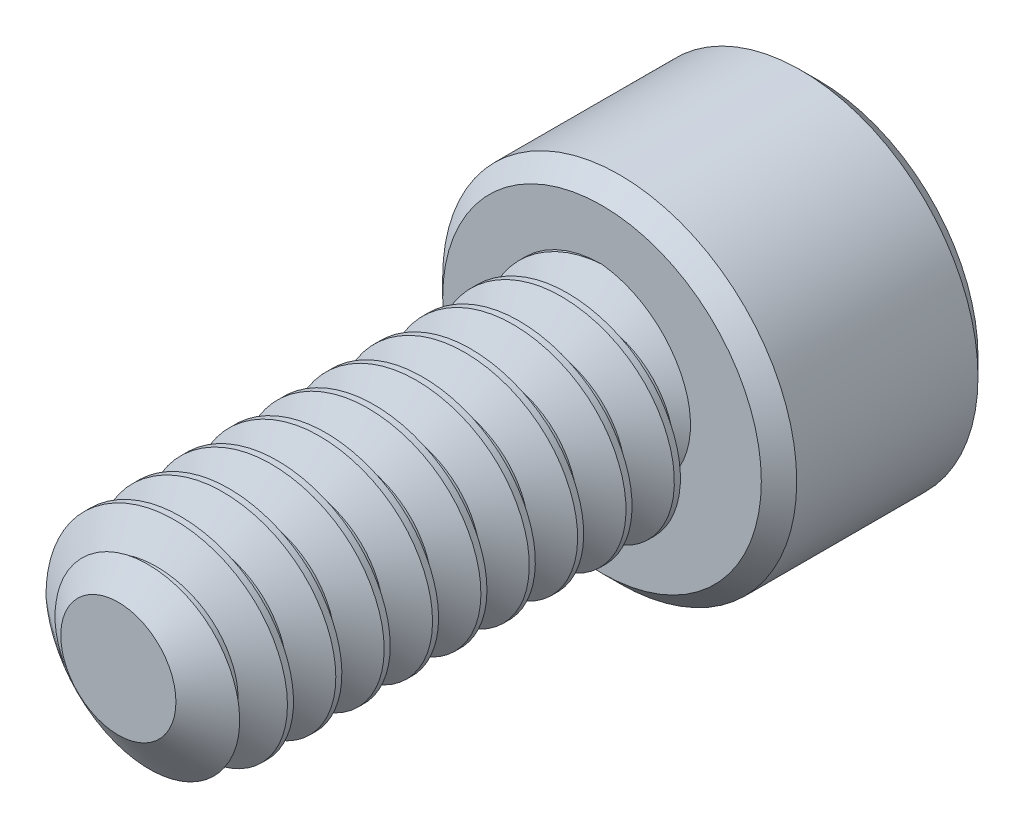
SolidWorks part; units mm, degrees
ref_plane "Front Plane" through (0, 0, 0) normal (0, 0, 1) x (1, 0, 0)
ref_plane "Top Plane" through (0, 0, 0) normal (0, 1, 0) x (1, 0, 0)
ref_plane "Right Plane" through (0, 0, 0) normal (1, 0, 0) x (0, 0, -1)
sketch "Sketch1" plane through (0, 0, 0) normal (0, 0, 1) x (1, 0, 0)
  circle A0 centre (0, 0) radius 1.4224
  dimension "OD" = 2.8448
extrude "Extrude1" add sketch "Sketch1" against normal blind 6.35
sketch "Sketch2" plane through (0, 0, 0) normal (0, 0, 1) x (1, 0, 0)
  circle A0 centre (0, 0) radius 1.4224 construction
  circle A1 centre (0, 0) radius 1.4224
curve "Helix/Spiral1" pitch 0.635 height 6.985 radius 1.4224 centre (0, 0, 0) axis (0, 0, -1) start towards (0, 1, 0) parameters "pitch"=0.635
sketch "Sketch3" plane through (0, 0, 0) normal (1, 0, 0) x (0, 0, -1)
  line L0 (-0.5556, 1.4224) -> (-0.3175, 1.01)
  line L1 (-0.3175, 1.01) -> (-0.2381, 1.01)
  line L2 (-0.2381, 1.01) -> (0, 1.4224)
  line L3 (-0.5556, 1.4224) -> (0, 1.4224)
  line L4 (-0.2778, 1.4224) -> (-0.2778, 1.01) construction
  line L5 (-0.4366, 1.2162) -> (-0.1191, 1.2162) construction
  line L6 (0, 1.4224) -> (0, -1.4224) construction
  dimension "D1" = 0.0794
  dimension "D2" = 0.3175
  dimension "D3" = 60
sweep "Cut-Sweep1" cut profiles "Sketch3" path "Helix/Spiral1"
sketch "Sketch4" plane through (0, 0, 0) normal (1, 0, 0) x (0, 0, -1)
  line L0 (0.4666, 1.4224) -> (0, 0.756)
  line L1 (0, 0.756) -> (0, 1.4224)
  line L2 (0.4666, 1.4224) -> (0, 1.4224)
  line L3 (-0.5556, 1.4224) -> (0, 1.4224) construction
  line L4 (0, 0) -> (7.0209, 0) construction
  dimension "D1" = 55
  dimension "D2" = 0.254
revolve "Cut-Revolve1" cut sketch "Sketch4" angle 360 about L4
sketch "Sketch5" plane through (0, 0, 0) normal (1, 0, 0) x (0, 0, -1)
  line L0 (6.35, -1.0232) -> (6.35, 1.0149) construction
  line L1 (6.35, 1.5494) -> (0.1202, 1.5494)
  line L2 (6.35, 1.5494) -> (6.35, 0)
  line L3 (6.35, 0) -> (0, 0)
  line L4 (0, 1.2192) -> (0, 0)
  line L5 (0.1202, 1.5494) -> (0, 1.2192)
  line L6 (0, 0) -> (9.9695, 0) construction
  point P3 (0, 1.5494)
  point P10 (0, 1.5494)
  dimension "D1" = 0.3302
  dimension "D2" = 0.127
  dimension "D3" = 20
  dimension "Min Thread" = 0
revolve "partially thread" [suppressed] add sketch "Sketch5" angle 360 about L6
sketch "Sketch6" plane through (0, 0, -6.35) normal (0, 0, -1) x (-1, 0, 0)
  circle A0 centre (0, 0) radius 2.3241
  dimension "head dia" = 4.6482
extrude "Extrude2" add sketch "Sketch6" along normal blind 2.8448
sketch "Sketch7" plane through (0, 0, -9.1948) normal (0, 0, -1) x (-1, 0, 0)
  line L1 (0, 1.3748) -> (-1.1906, 0.6874)
  line L2 (-1.1906, 0.6874) -> (-1.1906, -0.6874)
  line L3 (-1.1906, -0.6874) -> (0, -1.3748)
  line L4 (0, -1.3748) -> (1.1906, -0.6874)
  line L5 (1.1906, -0.6874) -> (1.1906, 0.6874)
  line L6 (1.1906, 0.6874) -> (0, 1.3748)
  circle A0 centre (0, 0) radius 1.1906 construction
  dimension "hex dia" = 2.3813
extrude "Cut-Extrude1" cut sketch "Sketch7" against normal blind 1.7859
sketch "Sketch8" plane through (0, 0, -9.1948) normal (0, 0, -1) x (-1, 0, 0)
  circle A0 centre (0, 0) radius 1.3748
extrude "Cut-Extrude2" cut sketch "Sketch8" against normal through all draft 45
chamfer "Chamfer1" distance 0.2324 angle 45 2 edges at (-2.3241, 0, -9.1948) (-2.3241, 0, -6.35)
sketch "Sketch9" plane through (0, 0, 0) normal (1, 0, 0) x (0, 0, -1)
  line L0 (0, 1.4224) -> (0, -1.4224) construction
  line L1 (1.5875, 1.4224) -> (1.5875, -1.4224) construction
  dimension "D1" = 1.5875
equation "\"D3@Helix/Spiral1\" = \"screw length@Extrude1\"+\"pitch@Helix/Spiral1\""
equation "\"D1@Sketch3\" = \"pitch@Helix/Spiral1\"*.125"
equation "\"D2@Sketch3\" = \"pitch@Helix/Spiral1\"*.5"
equation "\"D1@Cut-Extrude1\" = \"hex dia@Sketch7\"*.75"
equation "\"D1@Chamfer1\" = \"head dia@Sketch6\"*.05"
equation "\"D1@Sketch9\" = \"pitch@Helix/Spiral1\"*2.5"
